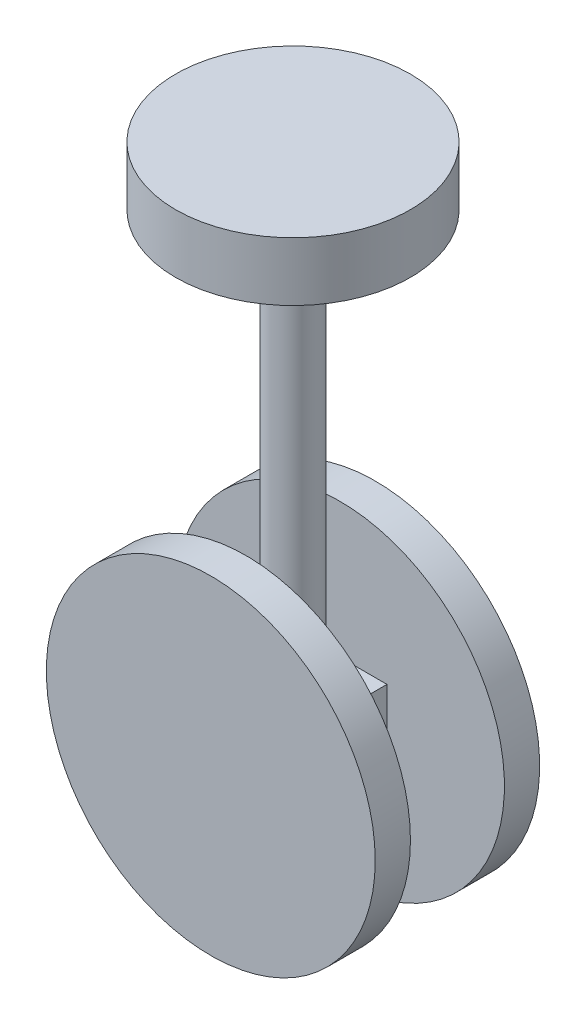
SolidWorks part; units mm, degrees
ref_plane "Front Plane" through (0, 0, 0) normal (0, 0, 1) x (1, 0, 0)
ref_plane "Top Plane" through (0, 0, 0) normal (0, 1, 0) x (1, 0, 0)
ref_plane "Right Plane" through (0, 0, 0) normal (1, 0, 0) x (0, 0, -1)
sketch "Sketch1" plane through (0, 0, 0) normal (0, 1, 0) x (1, 0, 0)
  circle A0 centre (0, 0) radius 10
extrude "Boss-Extrude1" add sketch "Sketch1" along normal blind 5
sketch "Sketch2" plane through (0, 0, 0) normal (0, -1, 0) x (1, 0, 0)
  circle A0 centre (0, 0) radius 2
extrude "Boss-Extrude2" add sketch "Sketch2" along normal blind 35
sketch "Sketch3" plane through (0, -35, 0) normal (0, -1, 0) x (1, 0, 0)
  line L0 (4, 4) -> (4, -4)
  line L2 (4, 4) -> (-4, 4)
  line L3 (-4, 4) -> (-4, -4)
  line L4 (-4, -4) -> (4, -4)
extrude "Boss-Extrude3" add sketch "Sketch3" along normal blind 5
sketch "Sketch5" plane through (0, 0, -4) normal (0, 0, -1) x (-1, 0, 0)
  circle A0 centre (0, -37.5) radius 14
  point P2 (0, 0)
sketch "Sketch6" plane through (0, 0, 4) normal (0, 0, 1) x (1, 0, 0)
  circle A0 centre (0, -37.5) radius 14
  point P2 (0, 0)
extrude "Boss-Extrude4" add sketch "Sketch5" along normal blind 3
extrude "Boss-Extrude5" add sketch "Sketch6" along normal blind 3 contours A0
